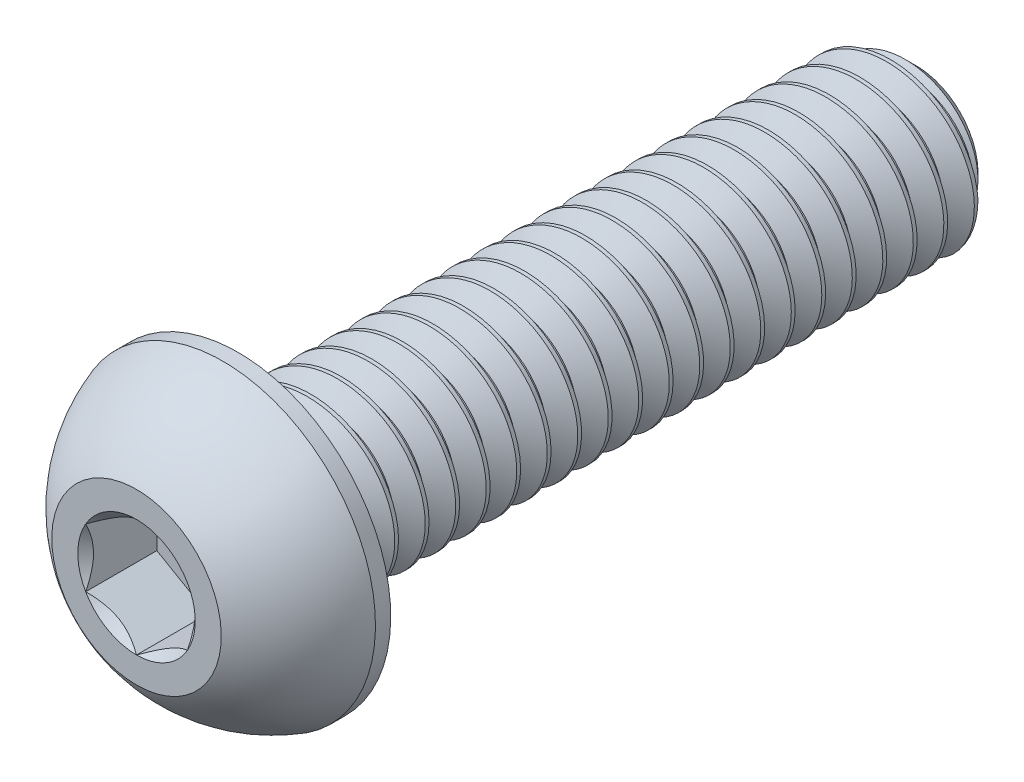
SolidWorks part; units mm, degrees
ref_plane "Front" through (0, 0, 0) normal (0, 0, 1) x (1, 0, 0)
ref_plane "Top" through (0, 0, 0) normal (0, 1, 0) x (1, 0, 0)
ref_plane "Right" through (0, 0, 0) normal (1, 0, 0) x (0, 0, -1)
sketch "Sketch1" plane through (0, 0, 0) normal (1, 0, 0) x (0, 0, -1)
  line L2 (-5, 1.25) -> (5, 1.25)
  line L3 (5, 1.25) -> (5, 0)
  line L4 (5, 0) -> (-5, 0)
  line L6 (-5.225, 2.25) -> (-5, 2.25) construction
  line L7 (5, 1.25) -> (5, -1.25) construction
  line L8 (-6.5, 0) -> (-5, 0) construction
  line L9 (-5, 2.25) -> (-5, -2.25) construction
  line L11 (-5, 1.25) -> (-5, 0)
  line L13 (-6.5, 0.75) -> (-6.5, -0.75) construction
  line L14 (-6.5, 0.75) -> (-6.5, 1.25) construction
  line L15 (4.9719, 1.2987) -> (5.1969, 0.909) construction
  line L16 (5.1969, 0.909) -> (5.4219, 1.2987) construction
  line L17 (5.4219, 1.2987) -> (4.9719, 1.2987) construction
  line L18 (5, 1.25) -> (5.3938, 1.25) construction
  line L19 (5.1969, 1.2987) -> (5.1969, 1.25) construction
  line L20 (5.1969, 1.25) -> (5.1969, 0.9577) construction
  line L21 (5.1969, 0.9577) -> (5.1969, 0.909) construction
  line L22 (5.1688, 0.9577) -> (5.225, 0.9577)
  line L23 (4.9859, 1.2744) -> (5.4078, 1.2744)
  line L24 (5.225, 0.9577) -> (5.4078, 1.2744)
  line L25 (5.1688, 0.9577) -> (4.9859, 1.2744)
  line L26 (4.6625, 1.25) -> (5, 0.9125)
  arc A3 (-6.5, 1.25) -> (-5.225, 2.25) centre (-4.49, 0) cw construction
  point P29 (5.1969, 1.2744)
  point P30 (3.875, -1.25)
  point P33 (0, 0)
  dimension "Thread Size" = 2.5
  dimension "D1" = 0.225
  dimension "Head Height" = 1.5
  dimension "Head Diameter" = 4.5
  dimension "Length" = 10
  dimension "Drive Size" = 1.5
  dimension "Thread Pitch" = 0.45
  dimension "D3" = 0.0563
  dimension "D2" = 0.3375
  dimension "D4" = 45
  dimension "D5" = 1.125
sketch "Sketch10" plane through (0, 0, 0) normal (1, 0, 0) x (0, 0, -1)
  line L0 (4.6625, 1.25) -> (5, 0.9125) construction
  line L1 (4.6625, 1.25) -> (5, 0.9125)
  line L4 (5, 1.25) -> (-5, 1.25)
  line L5 (5, 0) -> (5, 1.25)
  line L6 (-5, 0) -> (5, 0)
  line L7 (-5, 1.25) -> (-5, 0)
  line L8 (4.6625, 1.25) -> (-5, 1.25)
  line L9 (5, 0) -> (5, 0.9125)
  line L10 (-5, 0) -> (5, 0)
  line L11 (-5, 1.25) -> (-5, 0)
  dimension "D1" = 0
revolve "Revolve3" add sketch "Sketch10" angle 360 about L8
sketch "Sketch7" plane through (0, 0, 0) normal (1, 0, 0) x (0, 0, -1)
  line L6 (-5.225, 2.25) -> (-5, 2.25) construction
  line L8 (-6.5, 0) -> (-5, 0) construction
  line L11 (-5, 2.25) -> (-5, -2.25) construction
  line L12 (-5.225, 2.25) -> (-5, 2.25)
  line L13 (-6.5, 0) -> (-5, 0)
  line L14 (-6.5, 0.75) -> (-6.5, -0.75) construction
  line L15 (-5, 2.25) -> (-5, 0)
  line L16 (-6.5, 1.25) -> (-6.5, 0)
  arc A2 (-5.225, 2.25) -> (-6.5, 1.25) centre (-4.49, 0) ccw construction
  arc A3 (-5.225, 2.25) -> (-6.5, 1.25) centre (-4.49, 0) ccw
revolve "Revolve2" add sketch "Sketch7" angle 360 mid plane about L13
sketch "Sketch5" plane through (0, 0, 6.5) normal (0, 0, 1) x (1, 0, 0)
  line L1 (0.75, -0.433) -> (0.75, 0.433)
  line L2 (0.75, 0.433) -> (0, 0.866)
  line L3 (0, 0.866) -> (-0.75, 0.433)
  line L4 (-0.75, 0.433) -> (-0.75, -0.433)
  line L5 (-0.75, -0.433) -> (0, -0.866)
  line L6 (0, -0.866) -> (0.75, -0.433)
  circle A0 centre (0, 0) radius 0.75 construction
extrude "Cut-Extrude2" cut sketch "Sketch5" against normal blind 1.05
sketch "Sketch6" plane through (0, 0, 6.5) normal (0, 0, 1) x (1, 0, 0)
  circle A0 centre (0, 0) radius 0.866
extrude "Cut-Extrude3" cut sketch "Sketch6" against normal blind 1.05 draft 45
sketch "Sketch9" plane through (0, 0, 5) normal (0, 0, -1) x (-1, 0, 0)
  circle A0 centre (0, 0) radius 1.25 construction
  circle A4 centre (0, 0) radius 1.25
split "Split1" bodies to split 113 resulting bodies 123 124 split by face at (0, -2.25, 5)
sketch "Sketch11" plane through (0, 0, -5) normal (0, 0, -1) x (-1, 0, 0)
  circle A0 centre (0, 0) radius 1.25 construction
  circle A1 centre (0, 0) radius 1.25
curve "Helix/Spiral1" pitch 0.45 height 11.5 radius 1.25 centre (0, 0, -5) axis (0, 0, 1) start towards (0, 1, 0)
sketch "Sketch12" plane through (0, 0, 0) normal (1, 0, 0) x (0, 0, -1)
  line L0 (5.1688, 0.9577) -> (5.225, 0.9577) construction
  line L1 (5.225, 0.9577) -> (5.4078, 1.2744) construction
  line L2 (4.9859, 1.2744) -> (5.4078, 1.2744) construction
  line L3 (5.1688, 0.9577) -> (4.9859, 1.2744) construction
  line L4 (5.1688, 0.9577) -> (5.225, 0.9577)
  line L5 (5.225, 0.9577) -> (5.4078, 1.2744)
  line L6 (4.9859, 1.2744) -> (5.4078, 1.2744)
  line L7 (5.1688, 0.9577) -> (4.9859, 1.2744)
sweep "Cut-Sweep2" cut profiles "Sketch12" path "Helix/Spiral1" align with end faces yes
extrude "Boss-Extrude1" add sketch "Sketch9" along normal blind 10 draft 45
equation "\"D1@Cut-Extrude2\" = \"Head Height@Sketch1\" * .7"
equation "\"D1@Sketch1\" = \"Head Height@Sketch1\" * .15"
equation "\"D1@Cut-Extrude3\" = \"D1@Cut-Extrude2\""
equation "\"D3@Sketch1\" = \"Thread Pitch@Sketch1\" / 8"
equation "\"D2@Sketch1\" = \"Thread Pitch@Sketch1\" * 0.75"
equation "\"D3@Helix/Spiral1\" = \"Length@Sketch1\" + \"Head Height@Sketch1\""
equation "\"D4@Helix/Spiral1\" = \"Thread Pitch@Sketch1\""
equation "\"D5@Sketch1\" = \"Thread Pitch@Sketch1\" * 2.5"
